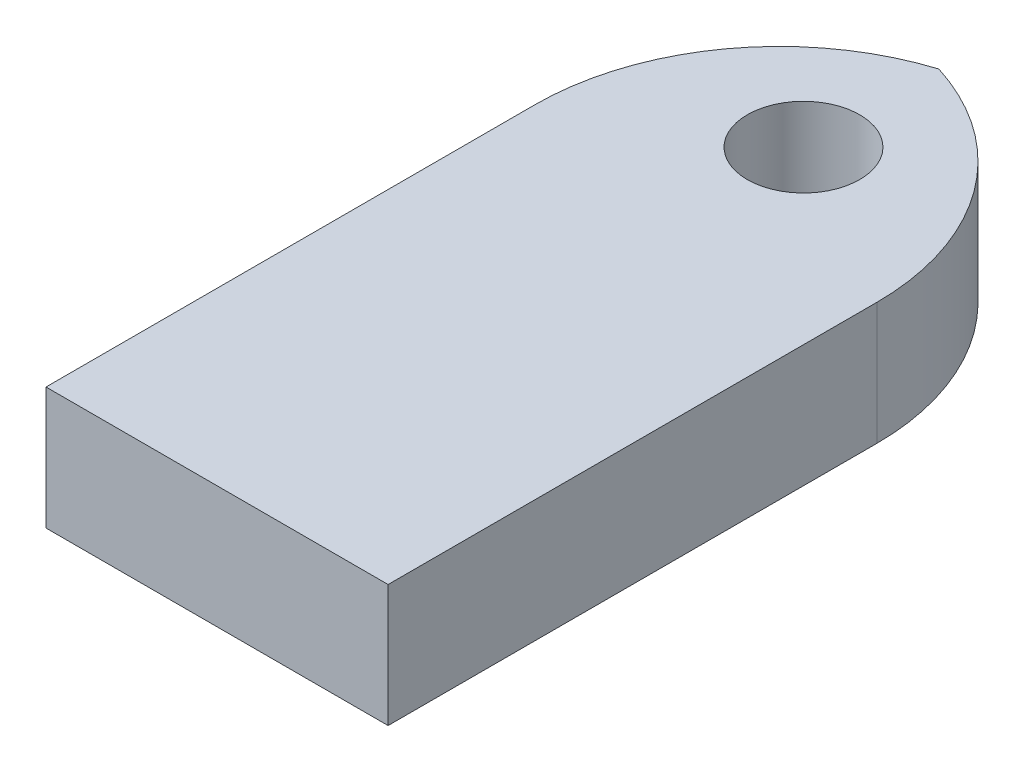
SolidWorks part; units mm, degrees
ref_plane "Front Plane" through (0, 0, 0) normal (0, 0, 1) x (1, 0, 0)
ref_plane "Top Plane" through (0, 0, 0) normal (0, 1, 0) x (1, 0, 0)
ref_plane "Right Plane" through (0, 0, 0) normal (1, 0, 0) x (0, 0, -1)
sketch "Sketch1" plane through (0, 0, 0) normal (0, 1, 0) x (1, 0, 0)
  line L1 (0, 0) -> (8.89, 0)
  line L2 (0, 0) -> (0, 19.05)
  line L3 (0, 19.05) -> (8.89, 19.05)
  line L4 (8.89, 0) -> (8.89, 19.05)
  circle A0 centre (4.445, 15.24) radius 1.4605
  dimension "D3" = 2.921
  dimension "D1" = 8.89
  dimension "D2" = 19.05
  dimension "D4" = 3.81
  dimension "D5" = 4.445
extrude "Boss-Extrude1" add sketch "Sketch1" along normal blind 3.175
fillet "Fillet1" radius 6.35 2 edges at (8.89, 1.5875, -19.05) (0, 1.5875, -19.05)
